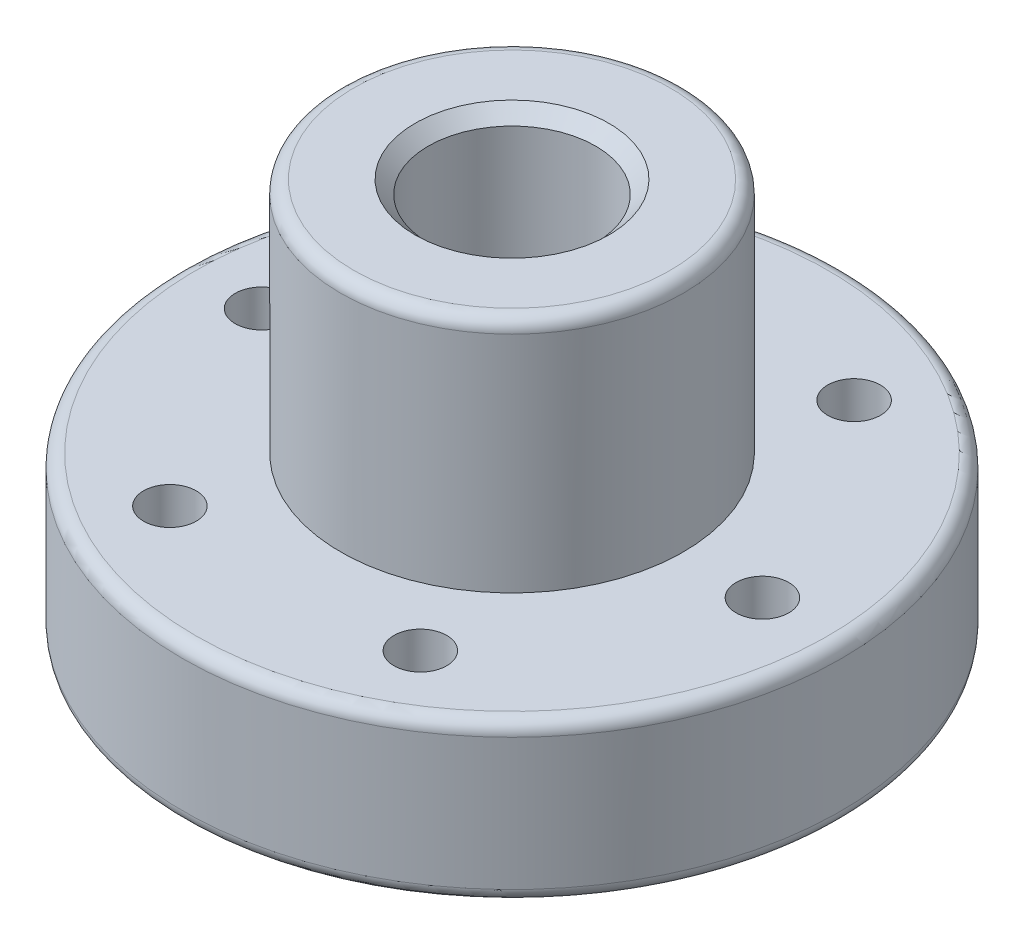
SolidWorks part; units mm, degrees
material "AISI 1035 Acier (SS)"
ref_plane "Plan de face" through (0, 0, 0) normal (0, 0, 1) x (1, 0, 0)
ref_plane "Plan de dessus" through (0, 0, 0) normal (0, 1, 0) x (1, 0, 0)
ref_plane "Plan de droite" through (0, 0, 0) normal (1, 0, 0) x (0, 0, -1)
sketch "Esquisse1" plane through (0, 0, 0) normal (0, 0, 1) x (1, 0, 0)
  line L0 (6.5, 15) -> (6.5, 6)
  line L1 (6.5, 6) -> (12.5, 6)
  line L2 (12.5, 6) -> (12.5, 0)
  line L9 (6.5, 15) -> (3.175, 15)
  line L10 (3.175, 15) -> (3.175, 0)
  line L11 (12.5, 0) -> (3.175, 0)
  line L12 (0, 0) -> (0, 15) construction
  dimension "D1" = 12.5
  dimension "D2" = 6
  dimension "D3" = 15
  dimension "D4" = 3.175
  dimension "D5" = 6
  dimension "D6" = 9.325
revolve "Révolution2" add sketch "Esquisse1" angle 360 about L12
sketch "Esquisse3" plane through (0, 6, 0) normal (0, 1, 0) x (1, 0, 0)
  line L0 (0, 0) -> (9.5, 0) construction
  circle A0 centre (9.5, 0) radius 1
  circle A2 centre (0, 0) radius 12.5 construction
  circle A3 centre (0, 0) radius 6.5 construction
  point P7 (6.5, 0)
  point P8 (12.5, 0)
  point P19 (0, 0)
  point P23 (0, -4.027)
  point P24 (0.0457, -3.8672)
  dimension "D1" = 2
  dimension "D3" = 3
  dimension "D2" = 3
extrude "Enlèv. mat.-Extru.1" cut sketch "Esquisse3" against normal through all
pattern_circular "Répétition circulaire1" count 6 over 360 about axis through (0, 0, 0) along (0, -1, 0) of "Enlèv. mat.-Extru.1"
fillet "Congé1" radius 0.5 3 edges at (0, 15, -6.5) (0, 0, -12.5) (0, 6, -12.5)
chamfer "Chanfrein1" distance 0.5 angle 45 2 edges at (0, 0, -3.175) (0, 15, -3.175)
